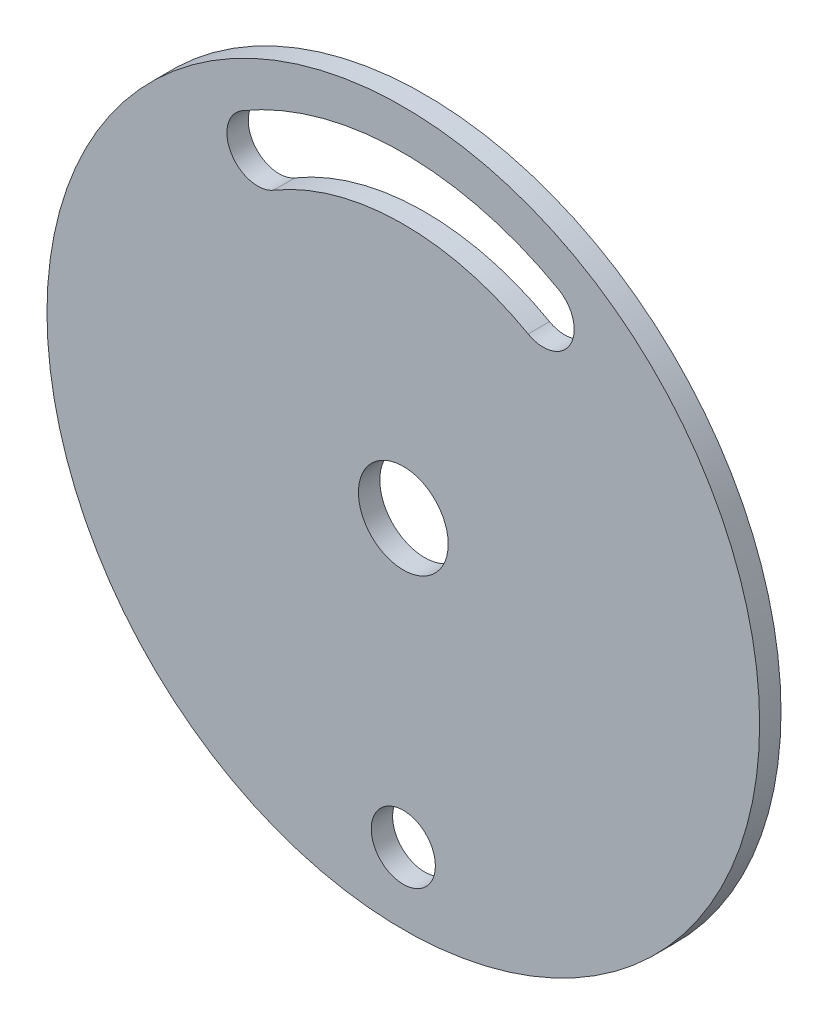
SolidWorks part; units mm, degrees
ref_plane "Front Plane" through (0, 0, 0) normal (0, 0, 1) x (1, 0, 0)
ref_plane "Top Plane" through (0, 0, 0) normal (0, 1, 0) x (1, 0, 0)
ref_plane "Right Plane" through (0, 0, 0) normal (1, 0, 0) x (0, 0, -1)
sketch "Sketch1" plane through (0, 0, 0) normal (0, 0, 1) x (1, 0, 0)
  line L0 (-27.0565, 7.3948) -> (22.9435, 7.3948) construction
  line L1 (-2.2565, 25.1948) -> (-2.2565, 29.5948) construction
  line L2 (-2.0565, 7.3948) -> (-2.2565, 25.1948)
  line L3 (-2.0565, 7.3948) -> (-11.1634, 22.7669)
  line L4 (-11.1634, 22.7669) -> (-13.3722, 26.4954)
  circle A0 centre (-2.0565, 7.3948) radius 25
  circle A2 centre (-2.0565, -12.6052) radius 2.25
  circle A7 centre (-2.0565, 7.3948) radius 3.15
  arc A9 (-11.1634, 22.7669) -> (-2.2565, 25.2609) centre (-2.0565, 7.3948) cw
  arc A10 (-2.2565, 29.5948) -> (-13.3722, 26.4954) centre (-2.0565, 7.3948) ccw
  arc A11 (-13.3722, 26.4954) -> (-11.1634, 22.7669) centre (-12.2678, 24.6312) ccw
  arc A12 (-2.3553, 29.5937) -> (8.8273, 26.7449) centre (-2.0565, 7.3948) cw
  arc A13 (6.7027, 22.9677) -> (-2.258, 25.2609) centre (-2.0565, 7.3948) ccw
  arc A14 (8.8273, 26.7449) -> (6.7027, 22.9677) centre (7.765, 24.8563) cw
  point P2 (-2.2565, 27.3948)
  dimension "D1" = 4.5
  dimension "D2" = 50
  dimension "D4" = 6.3
  dimension "D3" = 20
  dimension "D5" = 4.4
  dimension "D6" = 20
  dimension "D7" = 30
extrude "Boss-Extrude1" add sketch "Sketch1" along normal blind 1.5 contours A0 A2 A12 A14 A13 A9 A7 A11 A10 region at (-26.3494, 7.3948, 0)
